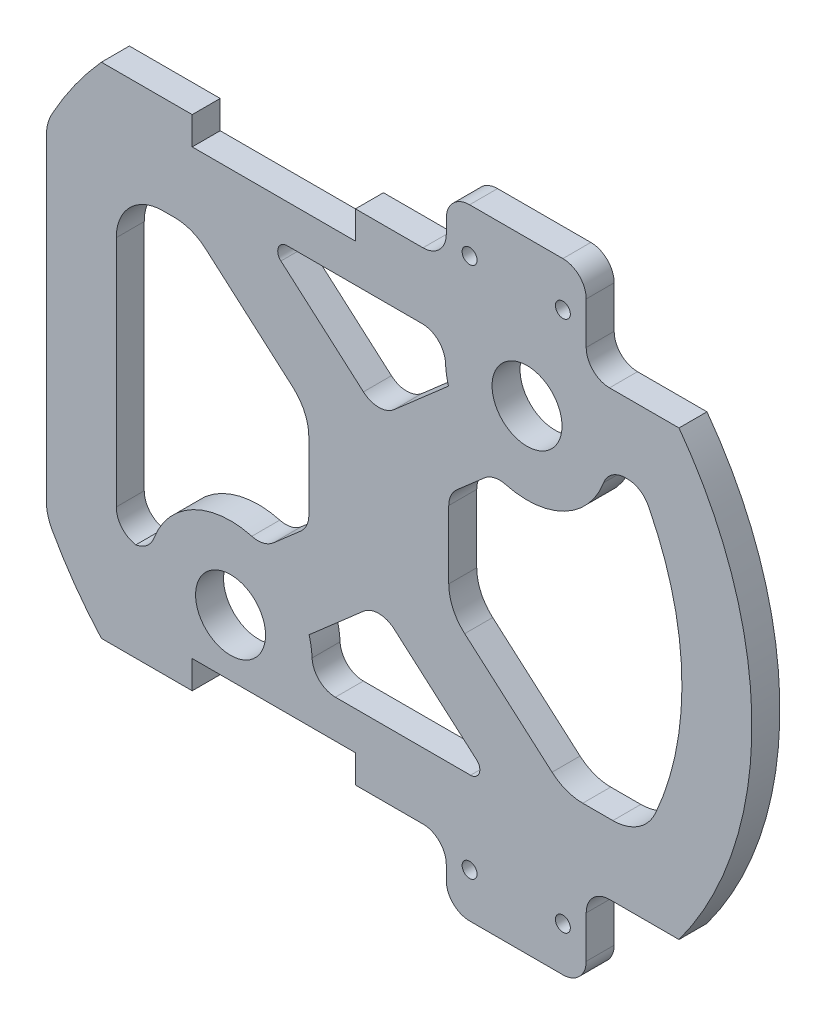
SolidWorks part; units mm, degrees
ref_plane "Plano frontal" through (0, 0, 0) normal (0, 0, 1) x (1, 0, 0)
ref_plane "Plano superior" through (0, 0, 0) normal (0, 1, 0) x (1, 0, 0)
ref_plane "Plano direito" through (0, 0, 0) normal (1, 0, 0) x (0, 0, -1)
sketch "Esboço1" plane through (0, 0, 0) normal (0, 0, 1) x (1, 0, 0)
  line L0 (80, 0) -> (0, 0) construction
  line L1 (-80, -66.5) -> (80, -66.5)
  line L2 (-80, -66.5) -> (-80, 66.5)
  line L3 (-80, 66.5) -> (80, 66.5)
  line L4 (80, -66.5) -> (80, 66.5)
  line L5 (-80, -66.5) -> (80, 66.5) construction
  line L6 (-80, 66.5) -> (80, -66.5) construction
  line L7 (80, 47.5) -> (-80, 47.5) construction
  line L8 (80, -47.5) -> (-80, -47.5) construction
  line L9 (14.4719, 66.5) -> (14.4719, 53.5)
  line L10 (0, 0) -> (0, 66.5) construction
  line L11 (44.4719, 66.5) -> (44.4719, 47.5)
  line L12 (-5.0035, -47.5) -> (-40.0035, -47.5)
  line L13 (14.4719, -66.5) -> (14.4719, -53.5)
  line L14 (44.4719, 47.5) -> (64.372, 47.5)
  line L15 (28.6277, 47.5) -> (28.6277, 66.5) construction
  line L16 (14.4719, 53.5) -> (-59.479, 53.5)
  line L17 (-40.0035, -53.5) -> (-40.0035, -47.5)
  line L18 (-31.7837, -35.2994) -> (31.7837, 35.2994) construction
  line L24 (-56.2917, 32.5) -> (-39.9802, 32.5)
  line L25 (-39.9802, 32.5) -> (-15, 10.6848)
  line L30 (-15, 10.6848) -> (-15, -10.6848)
  line L31 (-39.9802, -32.5) -> (-15, -10.6848)
  line L36 (-56.2917, -32.5) -> (-39.9802, -32.5)
  line L37 (56.2917, 32.5) -> (39.9802, 32.5)
  line L57 (39.9802, 32.5) -> (15, 10.6848)
  line L58 (15, 10.6848) -> (15, -10.6848)
  line L59 (39.9802, -32.5) -> (15, -10.6848)
  line L60 (56.2917, -32.5) -> (39.9802, -32.5)
  line L61 (-25, -39.3325) -> (0, -17.5)
  line L63 (-25, -39.3325) -> (25, -39.3325)
  line L64 (25, -39.3325) -> (0, -17.5)
  line L65 (-25, 39.3325) -> (0, 17.5)
  line L66 (25, 39.3325) -> (0, 17.5)
  line L67 (-25, 39.3325) -> (25, 39.3325)
  line L69 (-5.0035, -53.5) -> (-40.0035, -53.5)
  line L70 (-5.0035, 53.5) -> (-40.0035, 53.5)
  line L71 (-5.0035, 53.5) -> (-5.0035, 47.5)
  line L72 (-5.0035, 47.5) -> (-40.0035, 47.5)
  line L73 (-40.0035, 53.5) -> (-40.0035, 47.5)
  line L74 (-5.0035, 53.5) -> (-40.0035, 47.5) construction
  line L75 (-5.0035, 47.5) -> (-40.0035, 53.5) construction
  line L76 (-5.0035, -53.5) -> (-5.0035, -47.5)
  line L77 (14.4719, -53.5) -> (-59.479, -53.5)
  line L78 (44.4719, -66.5) -> (44.4719, -47.5)
  line L79 (44.4719, -47.5) -> (64.372, -47.5)
  line L80 (-71.2917, -36.2974) -> (-71.2917, 36.2974)
  line L81 (-56.2917, 32.5) -> (-56.2917, -32.5)
  circle A0 centre (0, 0) radius 80
  circle A1 centre (-31.7837, -35.2994) radius 7.5
  circle A2 centre (31.7837, 35.2994) radius 7.5
  circle A3 centre (19.4719, 57) radius 1.6
  circle A8 centre (19.4719, -57) radius 1.6
  arc A9 (-56.2917, -32.5) -> (-56.2917, 32.5) centre (0, 0) cw
  arc A11 (56.2917, -32.5) -> (56.2917, 32.5) centre (0, 0) ccw
  circle A12 centre (-31.7837, -35.2994) radius 17.5
  circle A13 centre (31.7837, 35.2994) radius 17.5
  circle A14 centre (39.4719, 57) radius 1.6
  circle A15 centre (39.4719, -57) radius 1.6
  point P0 (0, 0)
  point P37 (-22.5035, 50.5)
  point P38 (28.6277, 57)
  point P45 (-65, 0)
  point P63 (-59.1608, 33.8319)
  point P65 (-22.5035, 53.5)
  dimension "D6" = 15
  dimension "D7" = 3.2
  dimension "D18" = 15
  dimension "D9" = 15
  dimension "D11" = 35
  dimension "D1" = 95
  dimension "D2" = 19
  dimension "D3" = 160
  dimension "D4" = 95
  dimension "D5" = 48
  dimension "D8" = 15
  dimension "D10" = 30
  dimension "D12" = 30
  dimension "D13" = 35
  dimension "D14" = 5
  dimension "D15" = 50
  dimension "D16" = 5
  dimension "D17" = 6
  dimension "D19" = 35
  dimension "D21" = 15
extrude "Ressalto-extrusão1" add sketch "Esboço1" along normal blind 6 contours A0 L13 L1 L12 L17 L3 L9 A13 L37 A11 L60 L59 L58 L57 A12 L36 A9 L24 L25 L30 L31 A3 A14 A8 | L37 A13 L57 A2 | L57 A13 L37 | L67 A13 L66 | L61 A12 L31 A1 L36 L13 L63 | L31 A12 L36 | L63 A12 L61 | A9 L81 region at (6.2474, -0.5263, 0) region at (-47.0413, -42.87, 0) region at (-38.1575, -24.9182, 0) region at (-17.9859, -36.3042, 0) region at (-59.7958, 0, 0) region at (38.1575, 24.9182, 0) region at (44.5193, 32.9814, 0) region at (17.9859, 36.3042, 0)
fillet "Filete2" radius 10 8 edges at (56.2917, -32.5, 3) (39.9802, -32.5, 3) (15, -10.6848, 3) (-15, 10.6848, 3) (-39.9802, 32.5, 3) (-71.2917, -36.2974, 3) (-71.2917, 36.2974, 3) (-56.2917, 32.5, 3)
fillet "Filete3" radius 5 20 edges at (56.2917, 32.5, 3) (49.0584, 32.5, 3) (24.8078, 19.2499, 3) (15, 10.6848, 3) (-15, -10.6848, 3) (-24.8078, -19.2499, 3) (-49.0584, -32.5, 3) (14.7548, 39.3325, 3) (0, 17.5, 3) (0, -17.5, 3) (-14.7548, -39.3325, 3) (14.4719, 53.5, 3) (14.4719, -53.5, 3) (44.4719, -47.5, 3) (44.4719, 47.5, 3) (14.4719, -66.5, 3) (14.4719, 66.5, 3) (44.4719, 66.5, 3) (44.4719, -66.5, 3) (-56.2917, -32.5, 3)
fillet "Filete4" radius 2 2 edges at (25, -39.3325, 3) (-25, 39.3325, 3)
